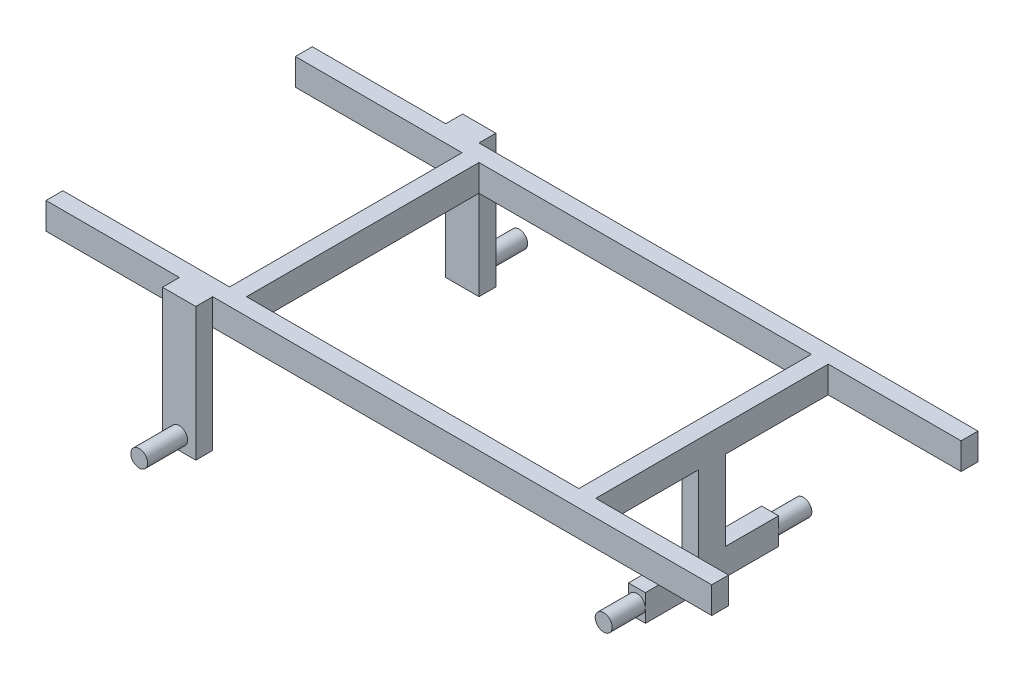
SolidWorks part; units mm, degrees
material "Bronce de aluminio"
ref_plane "Front" through (0, 0, 0) normal (0, 0, 1) x (1, 0, 0)
ref_plane "Top" through (0, 0, 0) normal (0, 1, 0) x (1, 0, 0)
ref_plane "Right" through (0, 0, 0) normal (1, 0, 0) x (0, 0, -1)
sketch "Croquis1" plane through (0, 0, 0) normal (0, 1, 0) x (1, 0, 0)
  line L0 (-1000, 349.2) -> (1000, 349.2)
  line L1 (-1000, -400) -> (1000, -400) construction
  line L2 (-1000, -400) -> (-1000, 400) construction
  line L3 (-1000, 400) -> (1000, 400) construction
  line L4 (1000, -400) -> (1000, 400) construction
  line L5 (-1000, -400) -> (1000, 400) construction
  line L6 (-1000, 400) -> (1000, -400) construction
  line L7 (-1000, -349.2) -> (1000, -349.2)
  line L8 (-1000, 349.2) -> (-1000, 400)
  line L9 (-1000, 400) -> (1000, 400)
  line L10 (1000, 400) -> (1000, 349.2)
  line L11 (-1000, -349.2) -> (-1000, -400)
  line L12 (-1000, -400) -> (1000, -400)
  line L13 (1000, -400) -> (1000, -349.2)
  line L14 (-499.2, 400) -> (-499.2, -400)
  line L15 (-448.4, 400) -> (-448.4, -400)
  line L16 (550, 400) -> (550, -400)
  line L17 (600.8, 400) -> (600.8, -400)
  line L18 (0, -349.2) -> (0, 349.2)
  line L19 (-499.2, -400) -> (-599.2, -400)
  line L20 (-499.2, -400) -> (-499.2, -450.8)
  line L21 (-499.2, -450.8) -> (-599.2, -450.8)
  line L22 (-599.2, -400) -> (-599.2, -450.8)
  line L23 (-499.2, 400) -> (-599.2, 400)
  line L24 (-499.2, 400) -> (-499.2, 450.8)
  line L25 (-499.2, 450.8) -> (-599.2, 450.8)
  line L26 (-599.2, 400) -> (-599.2, 450.8)
  line L27 (550, -40) -> (550, 40)
  line L28 (550, 40) -> (600.8, 40)
  line L29 (550, 40) -> (550, -40)
  line L30 (550, -40) -> (600.8, -40)
  line L31 (600.8, 40) -> (600.8, -40)
  line L32 (0, 0) -> (550, 0) construction
  line L33 (550, 200) -> (550, -200)
  line L34 (550, -200) -> (600.8, -200)
  line L35 (600.8, -200) -> (600.8, 200)
  line L36 (600.8, 200) -> (550, 200)
  point P0 (0, 0)
  point P34 (0, 0)
  dimension "D1" = 50.8
  dimension "D2" = 50.8
  dimension "D3" = 800
  dimension "D4" = 2000
  dimension "D5" = 50.8
  dimension "D6" = 50.8
  dimension "D7" = 1100
  dimension "D8" = 550
  dimension "D9" = 50.8
  dimension "D10" = 50.8
  dimension "D11" = 100
  dimension "D12" = 100
  dimension "D13" = 80
  dimension "D14" = 400
  dimension "D15" = 160
extrude "Saliente-Extruir1" add sketch "Croquis1" along normal blind 80 contours L14 L9 L8 L0 | L15 L9 L14 L0 | L16 L9 L15 L0 | L9 L17 L0 L10 | L17 L9 L16 L0 | L36 L17 L0 L16 | L17 L36 L16 L28 | L16 L30 L17 L28 | L16 L34 L17 L30 | L34 L16 L7 L17 | L17 L7 L16 L12 | L7 L17 L12 L13 | L16 L7 L15 L12 | L15 L7 L14 L12 | L14 L7 L11 L12 | L15 L0 L14 L7 | L26 L9 L24 L25 | L12 L22 L21 L20 region at (-749.6, 0, -374.6) region at (-473.8, 0, -374.6) region at (-473.8, 0, 0) region at (50.8, 0, -374.6) region at (-549.2, 0, -425.4) region at (-749.6, 0, 374.6) region at (-473.8, 0, 374.6) region at (50.8, 0, 374.6) region at (-549.2, 0, 425.4) region at (575.4, 0, -374.6) region at (575.4, 0, -274.6) region at (800.4, 0, -374.6) region at (575.4, 0, -120) region at (575.4, 0, 274.6) region at (575.4, 0, 374.6) region at (575.4, 0, 0) region at (800.4, 0, 374.6) region at (575.4, 0, 120)
extrude "Saliente-Extruir2" add sketch "Croquis1<4>" against normal blind 320 contours L12 L22 L21 L20 | L26 L9 L24 L25 | L16 L30 L17 L28 region at (-549.2, 0, -425.4) region at (-549.2, 0, 425.4) region at (575.4, 0, 0)
sketch "Croquis1<4>" plane through (0, 0, 0) normal (0, 1, 0) x (1, 0, 0) same geometry as "Croquis1"
extrude "Saliente-Extruir3" add sketch "Croquis1<5>" along normal blind 80 from surface contours L16 L34 L17 L30 | L16 L30 L17 L28 | L17 L36 L16 L28 region at (575.4, 0, -120) region at (575.4, 0, 0) region at (575.4, 0, 120) starting at face at (575.4, -320, 0)
sketch "Croquis1<5>" plane through (0, 0, 0) normal (0, 1, 0) x (1, 0, 0) same geometry as "Croquis1"
sketch "Croquis2" plane through (0, 0, 0) normal (0, 0, 1) x (1, 0, 0)
  line L0 (-499.2, -320) -> (-599.2, -320) construction
  line L2 (550, -240) -> (550, -320) construction
  line L3 (600.8, -240) -> (600.8, -320) construction
  line L4 (575.4, -320) -> (575.4, -240) construction
  line L5 (550, -320) -> (600.8, -320) construction
  line L6 (600.8, -240) -> (550, -240) construction
  line L7 (575.4, -240) -> (575.4, -280) construction
  line L9 (-599.2, 80) -> (-599.2, -320) construction
  line L10 (-599.2, -280) -> (-499.2, -280) construction
  line L11 (-499.2, 80) -> (-499.2, -320) construction
  circle A0 centre (-549.2, -280) radius 25.4
  circle A2 centre (575.4, -280) radius 25.4
  point P2 (0, 0)
  dimension "D1" = 40
  dimension "D2" = 50.8
  dimension "D3" = 50
extrude "Saliente-Extruir4" add sketch "Croquis2" along normal blind 120 from surface contours A0 starting at face at (-549.2, -120, 450.8)
extrude "Saliente-Extruir5" add sketch "Croquis2<7>" against normal blind 120 from surface contours A0 starting at face at (-549.2, -120, -450.8)
sketch "Croquis2<7>" plane through (0, 0, 0) normal (0, 0, 1) x (1, 0, 0) same geometry as "Croquis2"
extrude "Saliente-Extruir6" add sketch "Croquis2<8>" along normal mid plane 600 contours A2
sketch "Croquis2<8>" plane through (0, 0, 0) normal (0, 0, 1) x (1, 0, 0) same geometry as "Croquis2"
